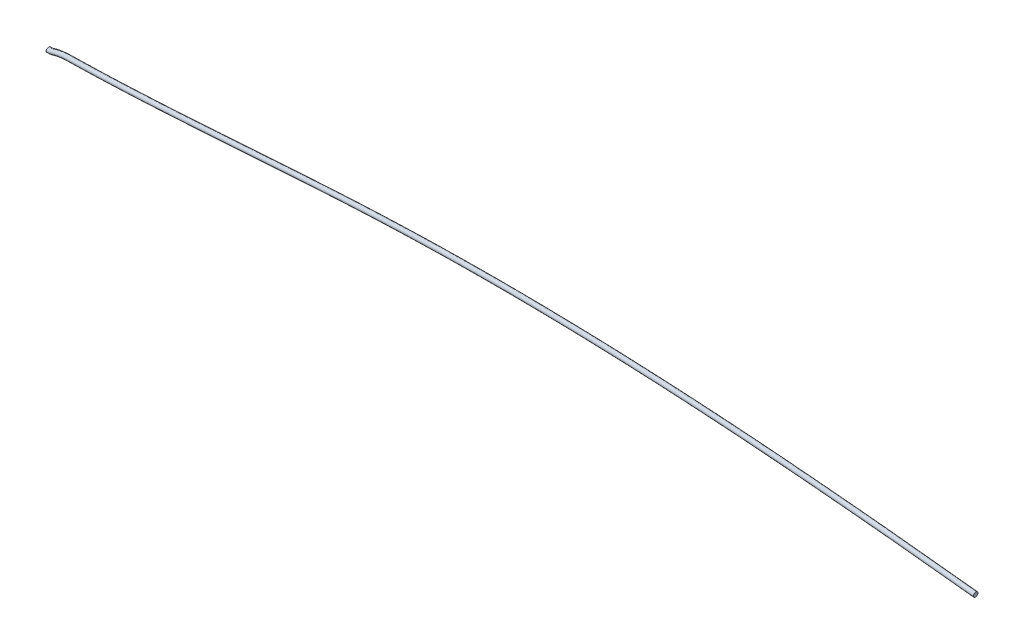
SolidWorks part; units mm, degrees
ref_plane "前视基准面" through (0, 0, 0) normal (0, 0, 1) x (1, 0, 0)
ref_plane "上视基准面" through (0, 0, 0) normal (0, 1, 0) x (1, 0, 0)
ref_plane "右视基准面" through (0, 0, 0) normal (1, 0, 0) x (0, 0, -1)
sketch "草图2" plane through (0, 0, 0) normal (0, 0, 1) x (1, 0, 0)
  spline S1 degree 3 poles (34.9465, 3.2388) (23.8739, 4.4483) (2.6584, 6.4489) (-29.4101, 6.8027) (-50.9038, 4.6058) (-62.5193, 4.4171) (-63.4312, 4.0891) (-63.6909, 4.1355) knots 0 0 0 0 0.337862 0.646847 0.971889 0.992026 1 1 1 1
sweep "扫描1" add path "草图2" circular profile diameter 0.5 parameters "D3"=0.5
